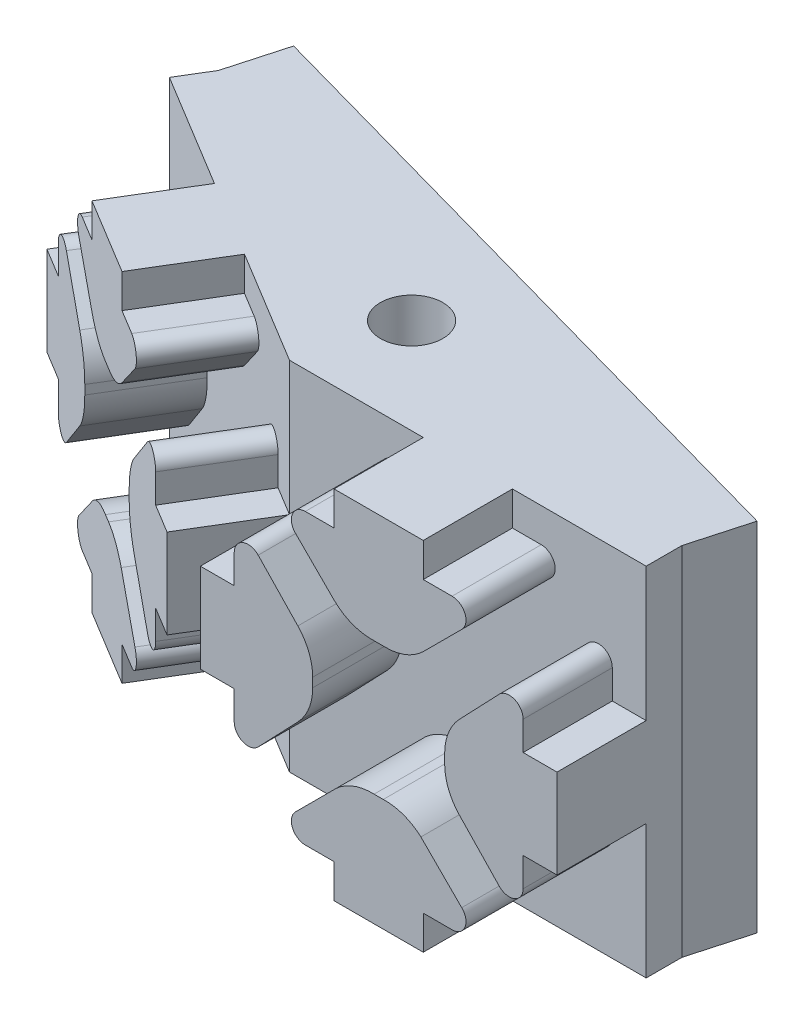
SolidWorks part; units mm, degrees
ref_plane "Ebene vorne" through (0, 0, 0) normal (0, 0, 1) x (1, 0, 0)
ref_plane "Ebene oben" through (0, 0, 0) normal (0, 1, 0) x (1, 0, 0)
ref_plane "Ebene rechts" through (0, 0, 0) normal (1, 0, 0) x (0, 0, -1)
sketch "Skizze1" plane through (0, 0, 0) normal (0, 0, 1) x (1, 0, 0)
  line L1 (0, 0) -> (20, 0)
  line L2 (0, 0) -> (0, 20)
  line L3 (0, 20) -> (20, 20)
  line L4 (20, 0) -> (20, 20)
  dimension "D1" = 20
extrude "Aufsatz-Linear austragen1" add sketch "Skizze1" along normal blind 2
sketch "Skizze2" plane through (0, 0, 2) normal (0, 0, 1) x (1, 0, 0)
  line L0 (10, 20) -> (10, 0) construction
  line L1 (20, 20) -> (0, 20) construction
  line L2 (0, 0) -> (20, 0) construction
  line L3 (0, 10) -> (20, 10) construction
  line L4 (0, 20) -> (0, 0) construction
  line L5 (20, 0) -> (20, 20) construction
  line L6 (12.5, 20) -> (7.5, 20)
  line L7 (12.5, 20) -> (12.5, 18.1)
  line L8 (12.5, 18.1) -> (14.1169, 18.1)
  line L9 (14.6561, 16.7564) -> (11.6497, 13.75)
  line L10 (5.3439, 16.7564) -> (8.3503, 13.75)
  line L11 (11.6497, 13.75) -> (8.3503, 13.75)
  line L12 (7.5, 18.1) -> (5.8831, 18.1)
  line L13 (7.5, 20) -> (7.5, 18.1)
  line L14 (10, 10) -> (20, 20) construction
  line L15 (20, 7.5) -> (18.1, 7.5)
  line L16 (18.1, 7.5) -> (18.1, 5.8831)
  line L17 (13.7, 10.2574) -> (13.7, 9.7426)
  line L18 (16.7564, 5.3439) -> (14.5322, 7.6688)
  line L19 (16.7564, 14.6561) -> (14.5322, 12.3312)
  line L20 (18.1, 12.5) -> (18.1, 14.1169)
  line L21 (20, 12.5) -> (18.1, 12.5)
  line L22 (20, 12.5) -> (20, 7.5)
  line L23 (7.5, 0) -> (7.5, 1.9)
  line L24 (7.5, 1.9) -> (5.8831, 1.9)
  line L25 (10.2574, 6.3) -> (9.7426, 6.3)
  line L26 (5.3439, 3.2436) -> (7.6337, 5.5334)
  line L27 (14.6561, 3.2436) -> (12.3663, 5.5334)
  line L28 (12.5, 1.9) -> (14.1169, 1.9)
  line L29 (12.5, 0) -> (12.5, 1.9)
  line L30 (12.5, 0) -> (7.5, 0)
  line L31 (0, 12.5) -> (0, 7.5)
  line L32 (0, 12.5) -> (1.9, 12.5)
  line L33 (1.9, 12.5) -> (1.9, 14.1169)
  line L34 (3.2436, 14.6561) -> (5.4678, 12.3312)
  line L35 (3.2436, 5.3439) -> (5.4678, 7.6688)
  line L36 (6.3, 10.2574) -> (6.3, 9.7426)
  line L37 (1.9, 7.5) -> (1.9, 5.8831)
  line L38 (0, 7.5) -> (1.9, 7.5)
  line L39 (10, 10) -> (0, 20) construction
  line L40 (9.7426, 13.7) -> (10.2574, 13.7)
  circle A0 centre (10, 10) radius 2.1
  arc A1 (1.9, 14.1169) -> (3.2436, 14.6561) centre (2.68, 14.1169) cw
  arc A2 (1.9, 5.8831) -> (3.2436, 5.3439) centre (2.68, 5.8831) ccw
  arc A3 (5.8831, 18.1) -> (5.3439, 16.7564) centre (5.8831, 17.32) ccw
  arc A4 (14.1169, 18.1) -> (14.6561, 16.7564) centre (14.1169, 17.32) cw
  arc A5 (18.1, 14.1169) -> (16.7564, 14.6561) centre (17.32, 14.1169) ccw
  arc A6 (18.1, 5.8831) -> (16.7564, 5.3439) centre (17.32, 5.8831) cw
  arc A7 (14.1169, 1.9) -> (14.6561, 3.2436) centre (14.1169, 2.68) ccw
  arc A8 (5.8831, 1.9) -> (5.3439, 3.2436) centre (5.8831, 2.68) cw
  arc A9 (5.4678, 12.3312) -> (6.3, 10.2574) centre (3.3, 10.2574) cw
  arc A10 (5.4678, 7.6688) -> (6.3, 9.7426) centre (3.3, 9.7426) ccw
  arc A13 (14.5322, 7.6688) -> (13.7, 9.7426) centre (16.7, 9.7426) cw
  arc A14 (14.5322, 12.3312) -> (13.7, 10.2574) centre (16.7, 10.2574) ccw
  arc A15 (7.6337, 5.5334) -> (9.7426, 6.3) centre (9.6387, 3.3018) cw
  arc A16 (12.3663, 5.5334) -> (10.2574, 6.3) centre (10.3613, 3.3018) ccw
  point P18 (10, 13.75)
  point P33 (13.75, 10)
  point P42 (10, 6.25)
  point P51 (6.25, 10)
  line M39 (0, 20) -> (0, 0)
  line M40 (0, 0) -> (20, 0)
  line M41 (20, 0) -> (20, 20)
  line M42 (20, 20) -> (0, 20)
  dimension "D1" = 4.2
  dimension "D6" = 0.78
  dimension "D4" = 3
  dimension "D2" = 5
  dimension "D3" = 1.9
  dimension "D5" = 45
  dimension "D7" = 6.25
extrude "Aufsatz-Linear austragen3" add sketch "Skizze2" along normal blind 5 contours A4 L8 L7 L13 L12 A3 L10 L11 L9 M42 | L35 A10 L36 A9 L34 A1 L33 L32 L38 L37 A2 M39 | L27 A16 L25 A15 L26 A8 L24 L23 L29 L28 A7 M40 | L19 A14 L17 A13 L18 A6 L16 L15 L21 L20 A5 M41 region at (10, 16.9101, 2) region at (16.9467, 10, 2) region at (3.0533, 10, 2) region at (10, 3.0749, 2)
fillet "Verrundung1" radius 3 2 edges at (11.6497, 13.75, 4.5) (8.3503, 13.75, 4.5)
ref_plane "Ebene1" through (0.5184, 0, 0.1449) normal (-0.9631, 0, -0.2691) x (-0.2691, 0, 0.9631)
mirror "Spiegeln1" about plane through (0.5184, 0, 0.1449) normal (-0.9631, 0, -0.2691) of "Verrundung1", "Aufsatz-Linear austragen3", "Aufsatz-Linear austragen1"
ref_plane "Ebene2" through (1.4486, 0, -5.1839) normal (0.2691, 0, -0.9631) x (-0.9631, 0, -0.2691)
ref_plane "Ebene3" through (2.3699, 0, -8.4809) normal (0.2691, 0, -0.9631) x (-0.9631, 0, -0.2691)
sketch "Skizze3" plane through (2.3699, 0, -8.4809) normal (0.2691, 0, -0.9631) x (-0.9631, 0, -0.2691)
  line L0 (-19.2621, 20) -> (-19.2621, 0)
  line L1 (-19.2621, 0) -> (18.1856, 0)
  line L2 (18.1856, 0) -> (18.1856, 20)
  line L3 (18.1856, 20) -> (-19.2621, 20)
extrude "Aufsatz-Linear austragen4" add sketch "Skizze3" against normal up to next
sketch "Skizze4" plane through (0, 0, 0) normal (0, -1, 0) x (1, 0, 0)
  line L0 (0, 2) -> (2.8883, -8.3361) construction
  line L1 (20.9213, -3.297) -> (-15.1448, -13.3752) construction
  circle A0 centre (1.4953, -3.3513) radius 1.75
  circle A1 centre (1.4953, -3.3513) radius 2.9
  dimension "D1" = 3.5
  dimension "D2" = 5.8
extrude "Schnitt-Linear austragen1" cut sketch "Skizze4" against normal through all contours A0 L0 | L0 A0 region at (2.2107, 0, -3.1514) region at (0.78, 0, -3.5512)
extrude "Schnitt-Linear austragen2" cut sketch "Skizze4<3>" against normal offset from surface (16 mm away) 4 up to face at (1.4953, 20, -5.1013)
sketch "Skizze4<3>" plane through (0, 0, 0) normal (0, -1, 0) x (1, 0, 0) same geometry as "Skizze4"
